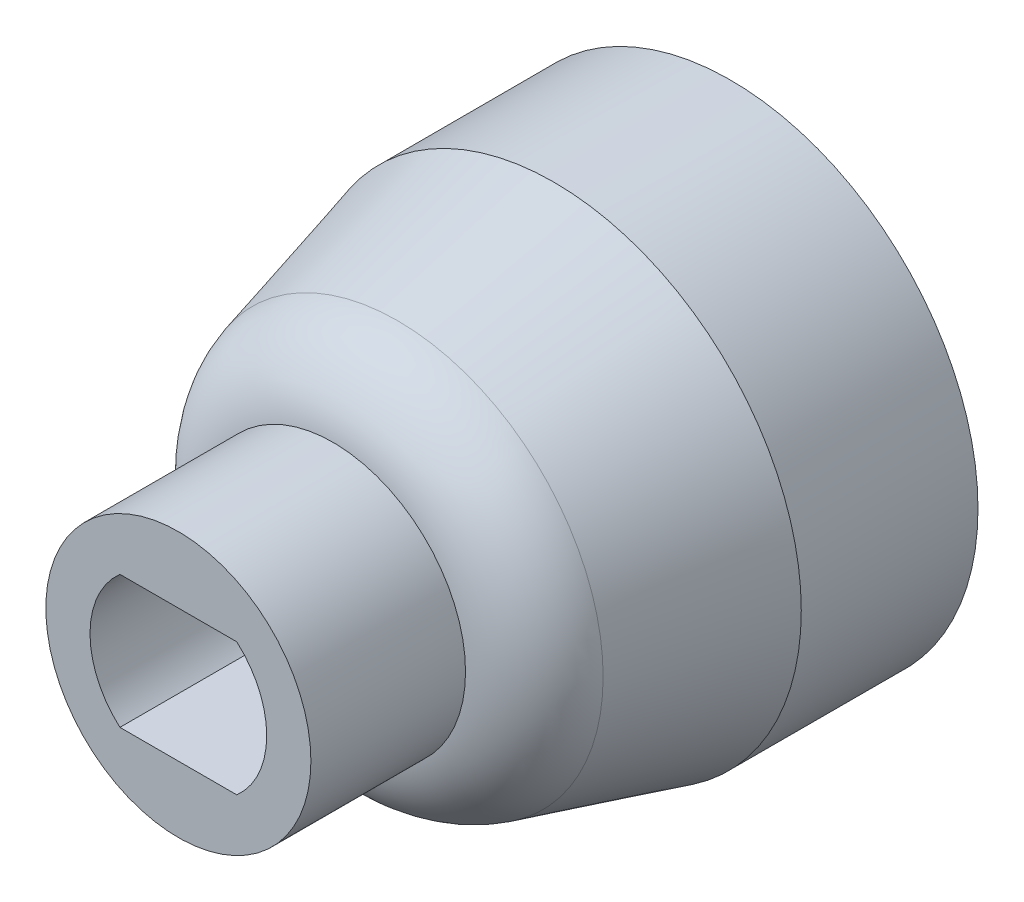
SolidWorks part; units mm, degrees
ref_plane "Front Plane" through (0, 0, 0) normal (0, 0, 1) x (1, 0, 0)
ref_plane "Top Plane" through (0, 0, 0) normal (0, 1, 0) x (1, 0, 0)
ref_plane "Right Plane" through (0, 0, 0) normal (1, 0, 0) x (0, 0, -1)
sketch "Sketch1" plane through (0, 0, 0) normal (0, 0, 1) x (1, 0, 0)
  circle A0 centre (0, 0) radius 5.6
  dimension "D1" = 11.2
extrude "Boss-Extrude1" add sketch "Sketch1" along normal blind 9
sketch "Sketch2" plane through (0, 0, 9) normal (0, 0, 1) x (1, 0, 0)
  line L0 (0, 1.5) -> (0, -1.5) construction
  line L1 (-1.3229, -1.5) -> (1.3229, -1.5)
  line L3 (-1.3229, 1.5) -> (1.3229, 1.5)
  circle A0 centre (0, 0) radius 3
  arc A1 (-1.3229, 1.5) -> (-1.3229, -1.5) centre (0, 0) ccw
  arc A2 (1.3229, -1.5) -> (1.3229, 1.5) centre (0, 0) ccw
  point P8 (0, 0)
  point P9 (0, -1.5)
  point P10 (0, 1.5)
  point P11 (0, 0)
  point P14 (0, 0)
  dimension "D1" = 6
  dimension "D2" = 4
  dimension "D3" = 3
extrude "Boss-Extrude2" add sketch "Sketch2" along normal blind 3.5
chamfer "Chamfer1" distance 5 angle 15 1 edges at (5.6, 0, 9) first distance on face at (5.6, 0, 9)
fillet "Fillet1" radius 2 1 edges at (4.2603, 0, 9)
